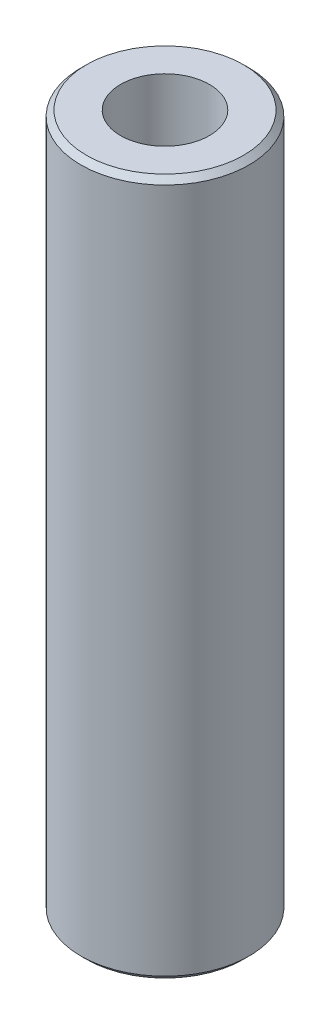
SolidWorks part; units mm, degrees
ref_plane "Front Plane" through (0, 0, 0) normal (0, 0, 1) x (1, 0, 0)
ref_plane "Top Plane" through (0, 0, 0) normal (0, 1, 0) x (1, 0, 0)
ref_plane "Right Plane" through (0, 0, 0) normal (1, 0, 0) x (0, 0, -1)
sketch "Sketch1" plane through (0, 0, 0) normal (0, 1, 0) x (1, 0, 0)
  circle A0 centre (0, 0) radius 22.5
  dimension "SHAFT_OD" = 45
extrude "Boss-Extrude1" add sketch "Sketch1" along normal blind 186.2898
sketch "Sketch2" plane through (0, 0, 0) normal (0, 1, 0) x (1, 0, 0)
  circle A0 centre (0, 0) radius 11.8876
  dimension "BORE_D" = 23.7752
extrude "Cut-Extrude1" cut sketch "Sketch2" along normal through all
chamfer "Chamfer1" distance 1.4892 angle 45 2 edges at (0, 186.2898, 22.5) (0, 0, 22.5)
